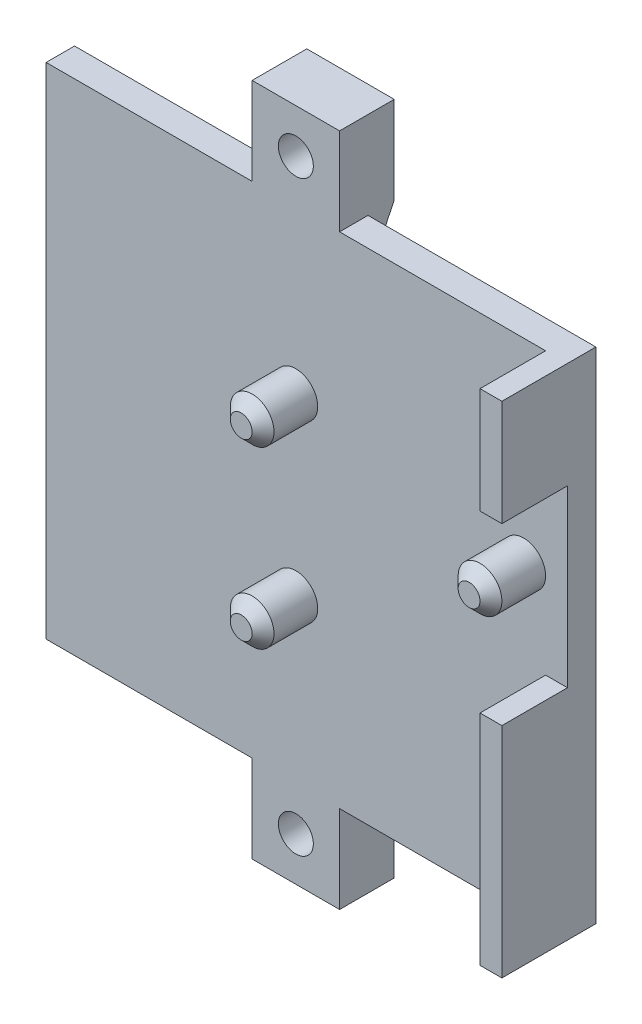
SolidWorks part; units mm, degrees
ref_plane "Front Plane" through (0, 0, 0) normal (1, 0, 0) x (0, 1, 0)
ref_plane "Top Plane" through (0, 0, 0) normal (0, 0, 1) x (0, 1, 0)
ref_plane "Right Plane" through (0, 0, 0) normal (0, 1, 0) x (-1, 0, 0)
sketch "Sketch2" plane through (0, 0, 0) normal (0, 0, 1) x (0, 1, 0)
  line L0 (-7.2, 11.5) -> (-7.2, -11.5)
  line L1 (-7.2, 11.5) -> (7.2, 11.5) construction
  line L2 (-7.2, 11.5) -> (-7.2, -11.5) construction
  line L3 (-7.2, -11.5) -> (7.2, -11.5) construction
  line L4 (7.2, 11.5) -> (7.2, -11.5) construction
  line L5 (-7.2, 11.5) -> (7.2, -11.5) construction
  line L6 (-7.2, -11.5) -> (7.2, 11.5) construction
  line L7 (-7.2, -11.5) -> (-4.8, -11.5)
  line L8 (-7.2, 11.5) -> (-4.8, 11.5)
  line L9 (-4.8, 11.5) -> (-4.8, 5.1)
  line L10 (0, 11.5) -> (0, -11.5) construction
  line L11 (7.2, 11.5) -> (7.2, -11.5) construction
  line L12 (4.8, 11.5) -> (4.8, 5.1)
  line L13 (7.2, 11.5) -> (4.8, 11.5)
  line L14 (7.2, -11.5) -> (4.8, -11.5)
  line L15 (7.2, 11.5) -> (7.2, -11.5)
  line L16 (-4.8, 5.1) -> (4.8, 5.1)
  line L17 (-4.8, -11.5) -> (-4.8, -10)
  line L18 (4.8, -11.5) -> (4.8, -10)
  line L19 (4.8, -10) -> (-4.8, -10)
  point P0 (0, 0)
  dimension "D1" = 14.4
  dimension "D2" = 23
  dimension "D3" = 2.4
  dimension "D4" = 6.4
  dimension "D5" = 1.5
extrude "Boss-Extrude1" add sketch "Sketch2" along normal blind 1
fillet "Fillet2" radius 1 8 edges at (11.5, -7.2, 0.5) (11.5, -4.8, 0.5) (11.5, 4.8, 0.5) (11.5, 7.2, 0.5) (-11.5, 7.2, 0.5) (-11.5, 4.8, 0.5) (-11.5, -7.2, 0.5) (-11.5, -4.8, 0.5)
sketch "Sketch3" plane through (0, 0, 1) normal (0, 0, 1) x (1, 0, 0)
  line L0 (-5.1, 0) -> (10, 0) construction
  line L1 (-5.1, 4.8) -> (-5.1, -4.8) construction
  line L2 (10, -4.8) -> (10, 4.8) construction
  line L4 (-2.55, 3.5) -> (7.45, 3.5)
  line L5 (-2.55, 3.5) -> (-2.55, -3.5)
  line L6 (-2.55, -3.5) -> (7.45, -3.5)
  line L7 (7.45, 3.5) -> (7.45, -3.5)
  line L8 (-2.55, 3.5) -> (7.45, -3.5) construction
  line L9 (-2.55, -3.5) -> (7.45, 3.5) construction
  point P6 (2.45, 0)
  dimension "D1" = 7
  dimension "D2" = 10
extrude "Boss-Extrude2" add sketch "Sketch3" along normal blind 2
sketch "Sketch4" plane through (0, 0, 3) normal (0, 0, 1) x (1, 0, 0)
  line L0 (2.45, 3.5) -> (2.45, -3.5) construction
  line L1 (7.45, 3.5) -> (-2.55, 3.5) construction
  line L2 (-2.55, -3.5) -> (7.45, -3.5) construction
  line L4 (-8.975, 11.425) -> (13.875, 11.425)
  line L5 (-8.975, 11.425) -> (-8.975, -11.425)
  line L6 (-8.975, -11.425) -> (13.875, -11.425)
  line L7 (13.875, 11.425) -> (13.875, -11.425)
  line L8 (-8.975, 11.425) -> (13.875, -11.425) construction
  line L9 (-8.975, -11.425) -> (13.875, 11.425) construction
  point P6 (2.45, 0)
  dimension "D1" = 22.85
extrude "Boss-Extrude3" add sketch "Sketch4" along normal blind 1.3
sketch "Sketch7" plane through (0, 0, 4.3) normal (0, 0, 1) x (1, 0, 0)
  line L0 (2.45, 11.425) -> (2.45, -11.425) construction
  line L1 (13.875, 11.425) -> (-8.975, 11.425) construction
  line L2 (-8.975, -11.425) -> (13.875, -11.425) construction
  line L3 (2.45, 11.425) -> (2.45, 13.425) construction
  line L4 (-8.975, 0) -> (13.875, 0) construction
  line L5 (0.45, 15.425) -> (4.45, 15.425)
  line L6 (0.45, 15.425) -> (0.45, 11.425)
  line L7 (0.45, 11.425) -> (4.45, 11.425)
  line L8 (4.45, 15.425) -> (4.45, 11.425)
  line L9 (0.45, 15.425) -> (4.45, 11.425) construction
  line L10 (0.45, 11.425) -> (4.45, 15.425) construction
  line L11 (-8.975, 11.425) -> (-8.975, -11.425) construction
  line L12 (13.875, -11.425) -> (13.875, 11.425) construction
  line L13 (0.45, -11.425) -> (4.45, -15.425) construction
  line L14 (0.45, -15.425) -> (4.45, -11.425) construction
  line L15 (2.45, -11.425) -> (2.45, -13.425) construction
  line L16 (4.45, -15.425) -> (4.45, -11.425)
  line L17 (0.45, -11.425) -> (4.45, -11.425)
  line L18 (0.45, -15.425) -> (0.45, -11.425)
  line L19 (0.45, -15.425) -> (4.45, -15.425)
  dimension "D1" = 2
extrude "Boss-Extrude4" add sketch "Sketch7" against normal blind 2.5
fillet "Fillet3" radius 10 1 edges at (2.45, 11.425, 3)
fillet "Fillet4" radius 10 1 edges at (2.45, -11.425, 3)
sketch "Sketch8" plane through (0, 0, 4.3) normal (0, 0, 1) x (1, 0, 0)
  line L0 (0.45, 13.425) -> (4.45, 13.425) construction
  line L1 (0.45, 15.425) -> (0.45, 11.425) construction
  line L2 (4.45, 11.425) -> (4.45, 15.425) construction
  line L3 (2.45, 13.425) -> (2.45, 15.425) construction
  line L4 (4.45, 15.425) -> (0.45, 15.425) construction
  line L5 (0.45, -13.425) -> (4.45, -13.425) construction
  line L6 (0.45, -11.425) -> (0.45, -15.425) construction
  line L7 (4.45, -15.425) -> (4.45, -11.425) construction
  line L8 (2.45, -15.425) -> (2.45, -13.425) construction
  line L9 (0.45, -15.425) -> (4.45, -15.425) construction
hole_wizard "Tap Drill for M2 Tap1" positions "Sketch9" profile "Sketch10" hole size "M2" standard "ISO" end condition through all
sketch "Sketch9" plane through (0, 0, 4.3) normal (0, 0, 1) x (1, 0, 0)
  point P0 (2.45, 13.425)
  point P3 (2.45, -13.425)
sketch "Sketch10" plane through (2.45, 13.425, 4.3) normal (1, 0, 0) x (0, -1, 0)
  line L0 (0, 0) -> (0, 4.3)
  line L1 (0, 4.3) -> (0.8, 4.3)
  line L2 (0.8, 4.3) -> (0.8, 0)
  line L5 (0.8, 0) -> (0, 0)
  line L11 (0, -6.35) -> (0, 107.95) construction
  dimension "Thru Hole Dia." = 1.6
  dimension "Thru Hole Depth" = 4.3
sketch "Sketch11" plane through (13.875, 0, 0) normal (1, 0, 0) x (0, 1, 0)
  line L1 (-11.425, 4.3) -> (11.425, 4.3)
  line L2 (-11.425, 4.3) -> (-11.425, 3)
  line L3 (-11.425, 3) -> (11.425, 3)
  line L4 (11.425, 4.3) -> (11.425, 3)
extrude "Boss-Extrude5" add sketch "Sketch11" along normal blind 1
sketch "Sketch12" plane through (0, 0, 4.3) normal (0, 0, 1) x (1, 0, 0)
  line L1 (14.875, -11.425) -> (13.875, -11.425)
  line L2 (14.875, -11.425) -> (14.875, -1.425)
  line L3 (14.875, -1.425) -> (13.875, -1.425)
  line L4 (13.875, -11.425) -> (13.875, -1.425)
  line L5 (14.875, 11.425) -> (13.875, 11.425)
  line L6 (14.875, 11.425) -> (14.875, 6.575)
  line L7 (14.875, 6.575) -> (13.875, 6.575)
  line L8 (13.875, 11.425) -> (13.875, 6.575)
  dimension "D1" = 10
  dimension "D2" = 1
  dimension "D3" = 8
  dimension "D4" = 1
extrude "Boss-Extrude6" add sketch "Sketch12" along normal blind 3
sketch "Sketch13" plane through (0, 0, 4.3) normal (0, 0, 1) x (1, 0, 0)
  line L0 (-8.975, 2.505) -> (14.875, 2.505) construction
  line L1 (-8.975, 11.425) -> (-8.975, -11.425) construction
  line L2 (14.875, 6.575) -> (14.875, -1.425) construction
  line L4 (-8.975, -11.425) -> (0.45, -11.425) construction
  line L5 (2.45, -46.275) -> (2.45, 15.425) construction
  line L7 (4.45, 15.425) -> (0.45, 15.425) construction
  line L8 (-8.975, 0) -> (2.45, 0) construction
  line L9 (2.45, 4) -> (2.45, -4)
  circle A0 centre (12.875, 2.505) radius 1
  circle A1 centre (2.45, 4) radius 1
  circle A2 centre (2.45, -4) radius 1
  point P13 (2.45, -15.425)
  point P21 (2.45, 0)
  dimension "D2" = 2
  dimension "D1" = 13.93
  dimension "D3" = 2
  dimension "D4" = 8
extrude "Boss-Extrude7" add sketch "Sketch13" along normal blind 2.5 contours A1 | A2 | A0 region at (3.1371, -3.3129, 4.3) region at (1.7629, 4.6871, 4.3) region at (12.875, 2.505, 4.3)
chamfer "Chamfer2" distance 0.5 angle 45 3 edges at (3.45, -4, 6.8) (13.875, 2.505, 6.8) (3.45, 4, 6.8)
